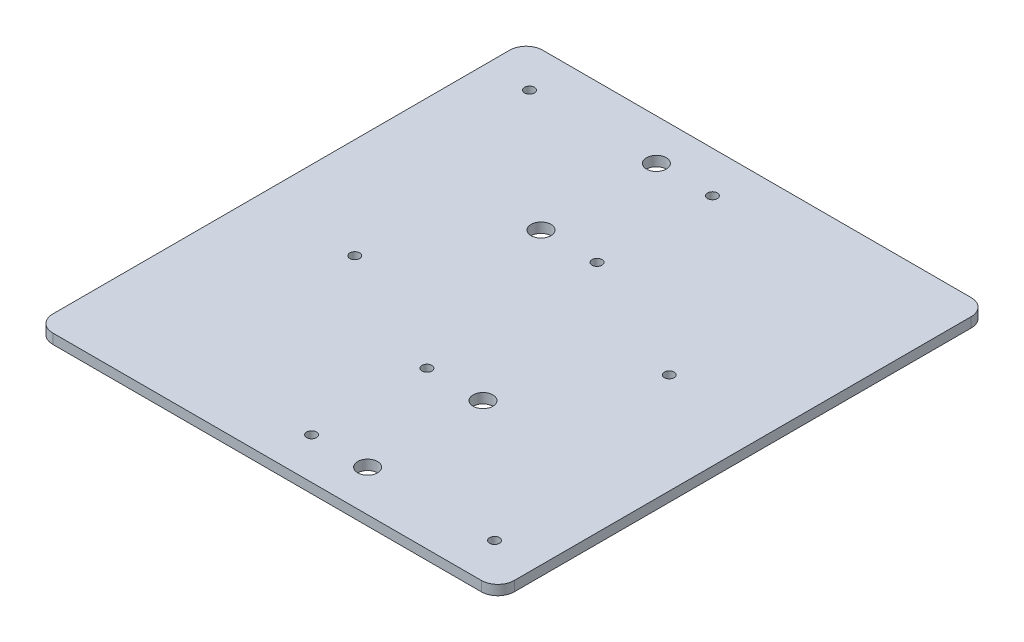
SolidWorks part; units mm, degrees
material "Pine"
ref_plane "Front Plane" through (0, 0, 0) normal (0, 0, 1) x (1, 0, 0)
ref_plane "Top Plane" through (0, 0, 0) normal (0, 1, 0) x (1, 0, 0)
ref_plane "Right Plane" through (0, 0, 0) normal (1, 0, 0) x (0, 0, -1)
sketch "Sketch1" plane through (0, 0, 0) normal (0, 1, 0) x (1, 0, 0)
  line L1 (70, -74.3) -> (-70, -74.3)
  line L2 (70, -74.3) -> (70, 74.3)
  line L3 (70, 74.3) -> (-70, 74.3)
  line L4 (-70, -74.3) -> (-70, 74.3)
  line L5 (70, -74.3) -> (-70, 74.3) construction
  line L6 (70, 74.3) -> (-70, -74.3) construction
  point P0 (0, 0)
  dimension "D1" = 140
  dimension "D2" = 148.6
extrude "Boss-Extrude1" add sketch "Sketch1" along normal blind 3
sketch "Sketch2" plane through (0, 3, 0) normal (0, 1, 0) x (1, 0, 0)
  line L4 (-70, 74.3) -> (-70, -74.3) construction
  line L6 (-1.65, 0) -> (1.65, 0) construction
  circle A0 centre (-18, 26.8) radius 3
  circle A1 centre (-18, 61.8) radius 3
  circle A2 centre (-1, 61.8) radius 1.5
  circle A3 centre (-1, 26.8) radius 1.5
  circle A11 centre (-56.5, 61.8) radius 1.5
  circle A13 centre (-39.5, -8.2) radius 1.5
  point P10 (0, 0)
  dimension "D1" = 6
  dimension "D2" = 6
  dimension "D3" = 3
  dimension "D4" = 3
  dimension "D21" = 3
  dimension "D27" = 3
  dimension "D5" = 35
  dimension "D6" = 35
  dimension "D7" = 61.8
  dimension "D9" = 13.5
  dimension "D11" = 17
  dimension "D12" = 70
  dimension "D13" = 17
extrude "Cut-Extrude1" cut sketch "Sketch2" against normal through all
fillet "Fillet1" radius 5 4 edges at (-70, 1.5, -74.3) (70, 1.5, -74.3) (70, 1.5, 74.3) (-70, 1.5, 74.3)
ref_axis "Axis1" through (0, -0.15, 0) along (0, 1, 0)
pattern_circular "CirPattern1" count 2 every 180 about axis through (0, -0.15, 0) along (0, 1, 0) of "Cut-Extrude1"
